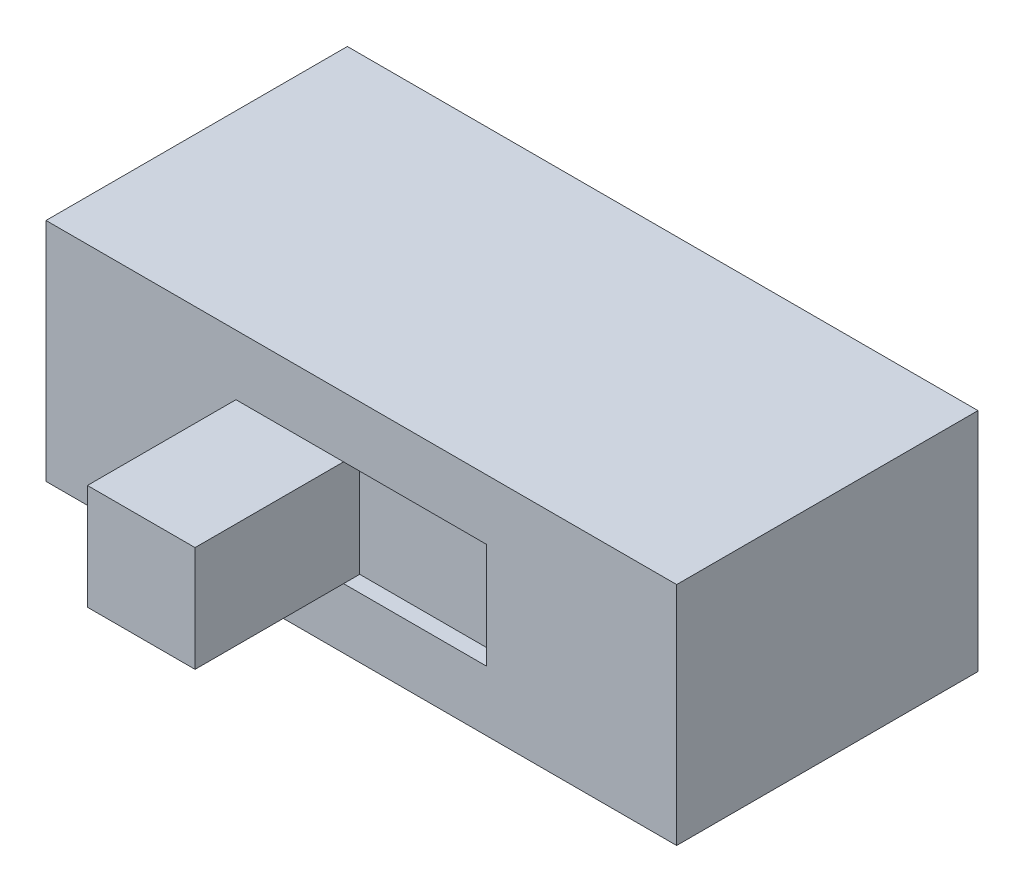
SolidWorks part; units mm, degrees
ref_plane "Front Plane" through (0, 0, 0) normal (0, 0, 1) x (1, 0, 0)
ref_plane "Top Plane" through (0, 0, 0) normal (0, 1, 0) x (1, 0, 0)
ref_plane "Right Plane" through (0, 0, 0) normal (1, 0, 0) x (0, 0, -1)
sketch "Sketch1" plane through (0, 0, 0) normal (0, 1, 0) x (1, 0, 0)
  line L1 (-5.86, 2.8) -> (5.86, 2.8)
  line L2 (-5.86, 2.8) -> (-5.86, -2.8)
  line L3 (-5.86, -2.8) -> (5.86, -2.8)
  line L4 (5.86, 2.8) -> (5.86, -2.8)
  line L5 (-5.86, 2.8) -> (5.86, -2.8) construction
  line L6 (-5.86, -2.8) -> (5.86, 2.8) construction
  point P0 (0, 0)
  dimension "D1" = 5.6
  dimension "D2" = 11.72
extrude "Boss-Extrude1" add sketch "Sketch1" along normal blind 4.2
sketch "Sketch2" plane through (0, 0, 2.8) normal (0, 0, 1) x (1, 0, 0)
  line L0 (-5.86, 2.1) -> (5.86, 2.1) construction
  line L1 (-2.33, 3.08) -> (-0.33, 3.08)
  line L2 (-2.33, 3.08) -> (-2.33, 1.12)
  line L3 (-2.33, 1.12) -> (-0.33, 1.12)
  line L4 (-0.33, 3.08) -> (-0.33, 1.12)
  line L5 (-2.33, 3.08) -> (-0.33, 1.12) construction
  line L6 (-2.33, 1.12) -> (-0.33, 3.08) construction
  line L7 (-5.86, 4.2) -> (-5.86, 0) construction
  line L8 (5.86, 4.2) -> (5.86, 0) construction
  line L9 (2.33, 2.4764) -> (5.86, 2.4764) construction
  line L10 (-0.33, 3.08) -> (2.33, 3.08)
  line L11 (-0.33, 3.08) -> (-0.33, 1.12)
  line L12 (-0.33, 1.12) -> (2.33, 1.12)
  line L13 (2.33, 3.08) -> (2.33, 1.12)
  line L14 (-2.33, 2.4764) -> (-5.86, 2.4764) construction
  point P0 (-1.33, 2.1)
  dimension "D1" = 1.96
  dimension "D2" = 2
  dimension "D3" = 3.53
extrude "Boss-Extrude2" add sketch "Sketch2" along normal blind 2.76 contours L4 L1 L2 L3 region at (-1.33, 2.1, 2.8)
extrude "Cut-Extrude1" cut sketch "Sketch2<3>" against normal blind 0.3 contours L13 L10 L4 L12 region at (1, 2.1, 2.8)
sketch "Sketch2<3>" plane through (0, 0, 2.8) normal (0, 0, 1) x (1, 0, 0) same geometry as "Sketch2"
